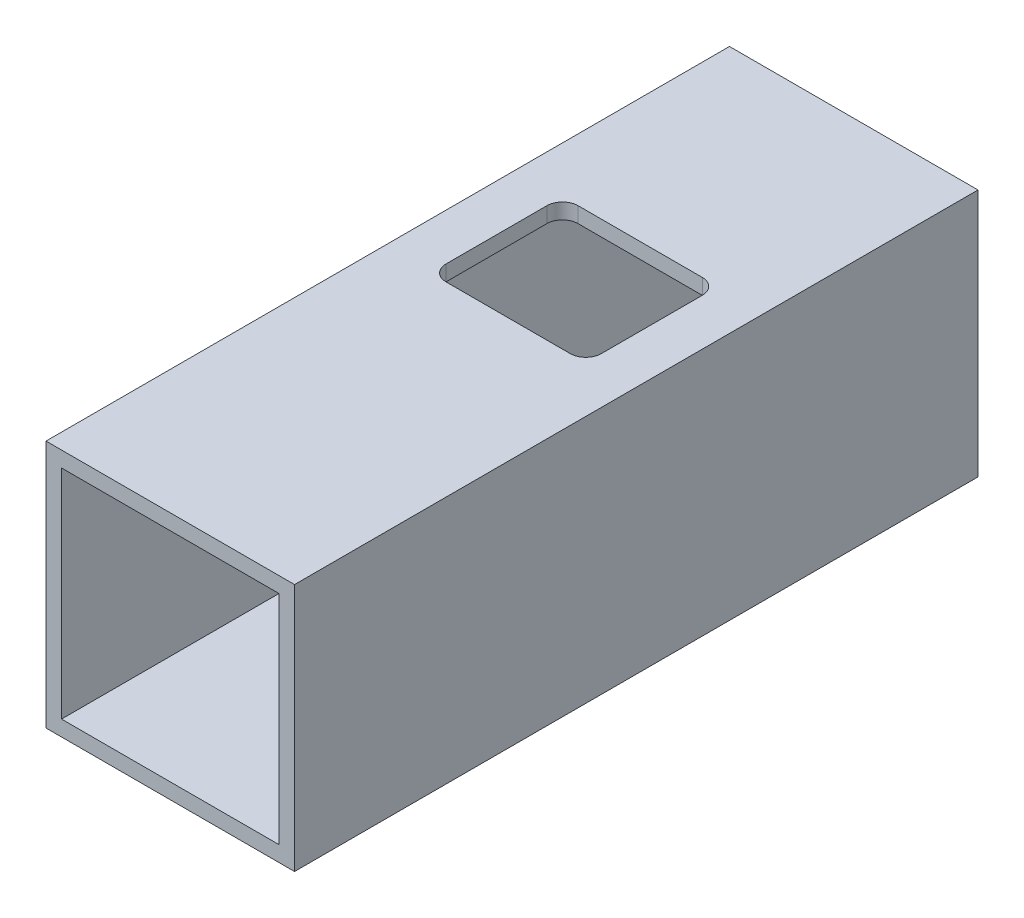
SolidWorks part; units mm, degrees
material "6061-T6 (SS)"
ref_plane "Front Plane" through (0, 0, 0) normal (0, 0, 1) x (1, 0, 0)
ref_plane "Top Plane" through (0, 0, 0) normal (0, 1, 0) x (1, 0, 0)
ref_plane "Right Plane" through (0, 0, 0) normal (1, 0, 0) x (0, 0, -1)
sketch "Sketch1" plane through (0, 0, 0) normal (0, 0, 1) x (1, 0, 0)
  line L1 (-25.4, -25.4) -> (25.4, -25.4)
  line L2 (-25.4, -25.4) -> (-25.4, 25.4)
  line L3 (-25.4, 25.4) -> (25.4, 25.4)
  line L4 (25.4, -25.4) -> (25.4, 25.4)
  line L5 (-25.4, -25.4) -> (25.4, 25.4) construction
  line L6 (-25.4, 25.4) -> (25.4, -25.4) construction
  point P0 (0, 0)
  dimension "D1" = 50.8
  dimension "D2" = 50.8
extrude "Boss-Extrude1" add sketch "Sketch1" along normal mid plane 139.7
shell "Shell1" thickness 3.175 removed face at (0, 0, -69.85) removed face at (0, 0, 69.85)
sketch "Sketch2" plane through (0, 0, 0) normal (0, 1, 0) x (1, 0, 0)
  line L0 (25.4, 69.85) -> (-25.4, 69.85) construction
  line L1 (15.875, 26.1938) -> (-15.875, 26.1938)
  line L2 (15.875, 26.1938) -> (15.875, -0.7937)
  line L3 (15.875, -0.7937) -> (-15.875, -0.7937)
  line L4 (-15.875, 26.1938) -> (-15.875, -0.7937)
  line L5 (25.4, -69.85) -> (-25.4, -69.85) construction
  point P4 (0, 26.1938)
  point P7 (0, 69.85)
  point P9 (15.875, 12.7)
  dimension "D1" = 31.75
  dimension "D2" = 26.9875
  dimension "D3" = 82.55
extrude "Cut-Extrude1" cut sketch "Sketch2" along normal through all
fillet "Fillet1" radius 3.175 4 edges at (15.875, 23.8125, -26.1938) (-15.875, 23.8125, -26.1938) (-15.875, 23.8125, 0.7937) (15.875, 23.8125, 0.7937)
